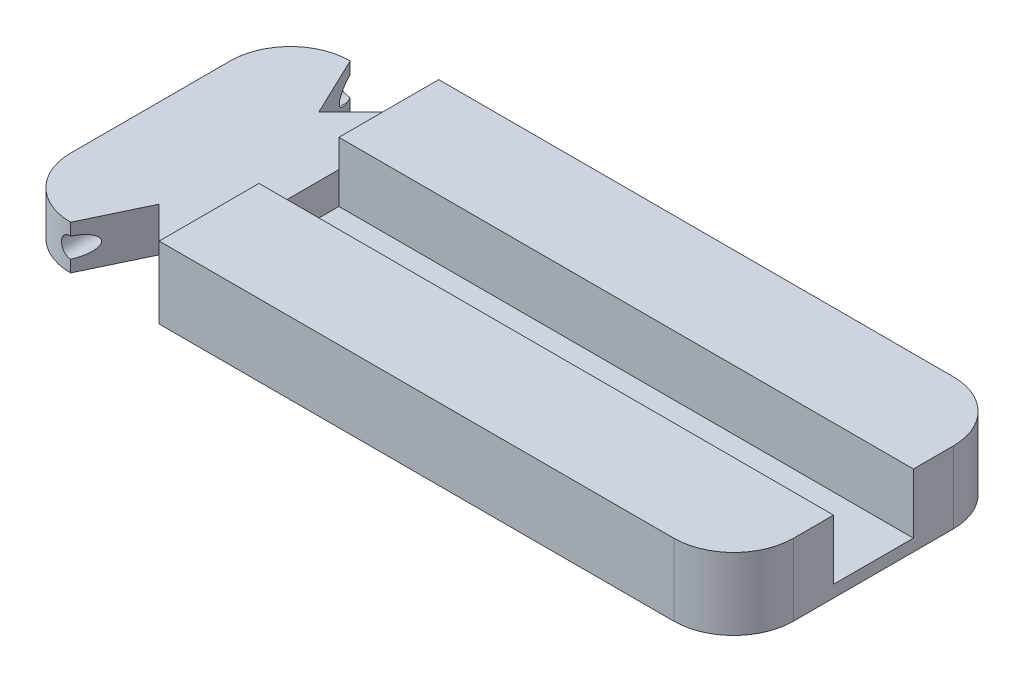
SolidWorks part; units mm, degrees
ref_plane "Front Plane" through (0, 0, 0) normal (0, 0, 1) x (1, 0, 0)
ref_plane "Top Plane" through (0, 0, 0) normal (0, 1, 0) x (1, 0, 0)
ref_plane "Right Plane" through (0, 0, 0) normal (1, 0, 0) x (0, 0, -1)
sketch "Sketch1" plane through (0, 0, 0) normal (0, 1, 0) x (1, 0, 0)
  line L0 (-90.5, 0) -> (90.5, 0) construction
  line L5 (0, 35) -> (0, -35) construction
  line L6 (-90.5, -20) -> (-90.5, 20)
  line L7 (90.5, 20) -> (90.5, -20)
  line L8 (-75.5, 35) -> (75.5, 35)
  line L9 (-75.5, -35) -> (75.5, -35)
  arc A0 (-75.5, 35) -> (-90.5, 20) centre (-75.5, 20) ccw
  arc A1 (-75.5, -35) -> (-90.5, -20) centre (-75.5, -20) cw
  arc A2 (75.5, -35) -> (90.5, -20) centre (75.5, -20) ccw
  arc A3 (75.5, 35) -> (90.5, 20) centre (75.5, 20) cw
  point P16 (-90.5, 35)
  dimension "D3" = 15
  dimension "D1" = 40
  dimension "D4" = 75.5
extrude "Boss-Extrude1" add sketch "Sketch1" along normal blind 18 contours A0 L6 A1 L9 A2 L7 A3 L8
sketch "Sketch3" plane through (0, 18, 0) normal (0, 1, 0) x (1, 0, 0)
  line L0 (-75.5, 35) -> (-68.3443, 20)
  line L1 (-75.5, 35) -> (75.5, 35) construction
  line L2 (-90.5, 0) -> (90.5, 0) construction
  line L3 (-90.5, -20) -> (-90.5, 20) construction
  line L4 (90.5, 20) -> (90.5, -20) construction
  line L5 (-75.5, -35) -> (-68.3443, -20)
  line L6 (-68.3443, -20) -> (-53.3443, -35)
  line L7 (-75.5, -35) -> (75.5, -35) construction
  line L8 (-68.3443, 20) -> (-53.3443, 35)
  line L9 (-75.5, 35) -> (-53.3443, 35)
  line L10 (-75.5, -35) -> (-53.3443, -35)
  dimension "D1" = 16.6194
  dimension "D2" = 64.497
  dimension "D3" = 15
extrude "Cut-Extrude1" cut sketch "Sketch3" against normal blind 18 contours L9 L8 L0
extrude "Cut-Extrude2" cut sketch "Sketch3<3>" against normal blind 18
sketch "Sketch3<3>" plane through (0, 18, 0) normal (0, 1, 0) x (1, 0, 0) same geometry as "Sketch3"
sketch "Sketch4" plane through (0, 18, 0) normal (0, 1, 0) x (1, 0, 0)
  line L0 (-53.3443, 35) -> (-53.3443, -35)
  line L1 (-53.3443, 35) -> (-98.4696, 35)
  line L2 (-98.4696, 35) -> (-98.4696, -35)
  line L3 (-98.4696, -35) -> (-53.3443, -35)
  dimension "D1" = 45.1253
extrude "Cut-Extrude3" cut sketch "Sketch4" against normal blind 7
sketch "Sketch5" plane through (0, 0, 35) normal (0, 0, 1) x (1, 0, 0)
  line L0 (-75.5, 11) -> (-75.5, 0) construction
  line L1 (-53.3443, 18) -> (-90.5, 18)
  line L2 (-53.3443, 18) -> (-53.3443, 0)
  line L3 (-53.3443, 0) -> (-90.5, 0)
  line L4 (-90.5, 18) -> (-90.5, 0)
  circle A0 centre (-75.5, 5.5) radius 2.5
  point P8 (-75.5, 5.5)
  dimension "D1" = 5
extrude "Cut-Extrude4" cut sketch "Sketch5" against normal up to surface (70 mm away) contours A0 up to face at (-1.8066, 9.4, -35)
sketch "Sketch6" plane through (0, 18, 0) normal (0, 1, 0) x (1, 0, 0)
  line L0 (-53.3443, -35) -> (-53.3443, 35) construction
  line L1 (-53.3443, 10) -> (90.5, 10)
  line L2 (-53.3443, 10) -> (-53.3443, -10)
  line L3 (-53.3443, -10) -> (90.5, -10)
  line L4 (90.5, 10) -> (90.5, -10)
  line L5 (90.5, 20) -> (90.5, -20) construction
  line L6 (-53.3443, 0) -> (90.5, 0) construction
  point P10 (0, 0)
  point P11 (-53.3443, 0)
  dimension "D1" = 20
extrude "Cut-Extrude5" cut sketch "Sketch6" against normal blind 15
equation "\"hole_size\"= 5mm"
